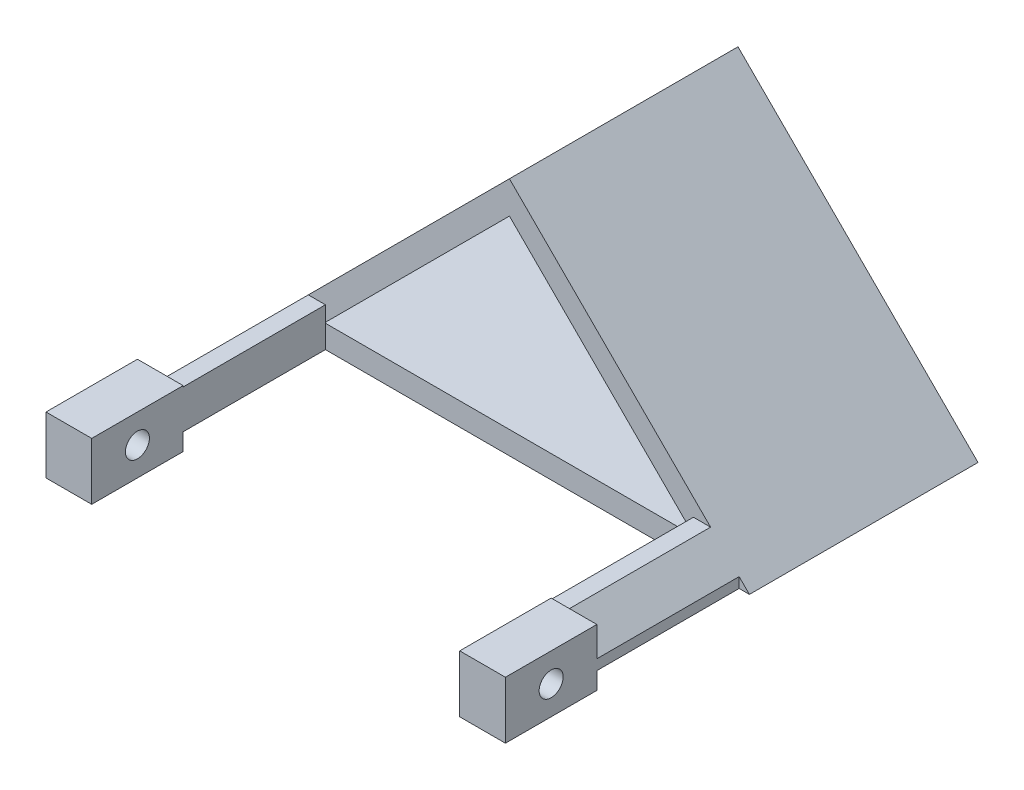
SolidWorks part; units mm, degrees
ref_plane "Front Plane" through (0, 0, 0) normal (0, 0, 1) x (1, 0, 0)
ref_plane "Top Plane" through (0, 0, 0) normal (0, 1, 0) x (1, 0, 0)
ref_plane "Right Plane" through (0, 0, 0) normal (1, 0, 0) x (0, 0, -1)
sketch "Sketch1" plane through (0, 0, 0) normal (0, 0, 1) x (1, 0, 0)
  line L1 (0, 0) -> (-42, -42)
  line L2 (0, -1000.3549) -> (0, 48999.6451) construction
  line L3 (-32.3431, -38) -> (0, -5.6569)
  line L4 (32.3431, -38) -> (0, -5.6569)
  line L5 (0, 0) -> (42, -42)
  line L7 (-42, -42) -> (42, -42)
  line L8 (-32.3431, -38) -> (32.3431, -38)
  line L9 (-34, -34) -> (34, -34) construction
  dimension "D1" = 90
  dimension "D2" = 4
  dimension "D3" = 4
  dimension "D4" = 68
  dimension "D5" = 8
extrude "Boss-Extrude1" add sketch "Sketch1" along normal mid plane 40
sketch "Sketch2" plane through (0, 0, 0) normal (1, 0, 0) x (0, 0, -1)
  line L0 (0, -1034.3624) -> (0, 48965.6376) construction
  line L1 (-20, -42) -> (20, -42) construction
  line L2 (-3.5, -42) -> (-3.5, -65.5)
  line L3 (-3.5, -65.5) -> (-9, -65.5)
  line L4 (-9, -65.5) -> (-9, -69)
  line L5 (-9, -69) -> (9, -69)
  line L6 (9, -65.5) -> (9, -69)
  line L7 (3.5, -65.5) -> (9, -65.5)
  line L8 (3.5, -42) -> (3.5, -65.5)
  line L9 (3.5, -42) -> (-3.5, -42)
  point P5 (0, -42)
  dimension "D1" = 7
  dimension "D2" = 3.5
  dimension "D3" = 27
  dimension "D4" = 18
extrude "Boss-Extrude2" [suppressed] add sketch "Sketch2" along normal blind 6 from vertex starting at point (-42, -42, 0)
sketch "Sketch4" [suppressed] plane through (0, 0, 0) normal (1, 0, 0) x (0, 0, -1)
  line L0 (-20, -38.4859) -> (20, -38.4859) construction
  line L1 (3.5, -38.4859) -> (13.5, -38.4859)
  line L2 (3.5, -38.4859) -> (3.5, -65.4859)
  line L3 (3.5, -65.4859) -> (13.5, -65.4859)
  line L4 (13.5, -38.4859) -> (13.5, -65.4859)
  line L5 (-9, -65.4859) -> (9, -65.4859) construction
  line L7 (-11, -38.4859) -> (-18.5, -38.4859)
  line L8 (-11, -38.4859) -> (-11, -65.4859)
  line L9 (-11, -65.4859) -> (-18.5, -65.4859)
  line L10 (-18.5, -38.4859) -> (-18.5, -65.4859)
  line L11 (-9, -61.9859) -> (-9, -65.4859) construction
  dimension "D1" = 10
  dimension "D2" = 2
  dimension "D3" = 7.5
extrude "Boss-Extrude3" [suppressed] add sketch "Sketch4" against normal blind 6 from vertex starting at point (42, -42, 20)
sketch "Sketch5" plane through (0, 0, 20) normal (0, 0, 1) x (1, 0, 0)
  line L1 (0, 0) -> (-42, -42) construction
  line L2 (-35.2, -35.2) -> (-32.2, -35.2)
  line L3 (-32.2, -35.2) -> (-32.2, -42)
  line L4 (-42, -42) -> (42, -42) construction
  line L5 (-32.2, -42) -> (-40.2, -42)
  line L6 (-40.2, -42) -> (-40.2, -40.2)
  line L7 (-40.2, -40.2) -> (-35.2, -35.2)
  line L9 (-40.4, 34.5736) -> (-40.4, -70) construction
  point P5 (-28.1785, -42)
  point P10 (-28.3963, -42)
  point P11 (0, 0)
  dimension "D1" = 8
  dimension "D2" = 3
  dimension "D3" = 0.2
extrude "Boss-Extrude4" add sketch "Sketch5" along normal up to surface (24.9 mm away)
sketch "Sketch6" plane through (0, 0, 44.9) normal (0, 0, 1) x (1, 0, 0)
  line L0 (-40.2, -40.2) -> (-40.2, -42) construction
  line L1 (-32.2, -45) -> (-40.2, -45)
  line L2 (-32.2, -45) -> (-32.2, -35)
  line L3 (-32.2, -35) -> (-40.2, -35)
  line L4 (-40.2, -45) -> (-40.2, -35)
  line L5 (-32.2, -42) -> (-32.2, -35.2) construction
  line L6 (-40.2, -42) -> (-32.2, -42) construction
  point P5 (-31.136, -51.2284)
  point P6 (-30.277, -57.4758)
  point P7 (0, 0)
  point P10 (-32.9605, -43.2167)
  dimension "D1" = 10
  dimension "D2" = 3
extrude "Boss-Extrude5" add sketch "Sketch6" along normal blind 16
sketch "Sketch7" plane through (-32.2, 0, 0) normal (1, 0, 0) x (0, 0, -1)
  line L0 (-60.9, -35) -> (-44.9, -35) construction
  line L1 (-60.9, -45) -> (-60.9, -35) construction
  circle A0 centre (-52.9, -40) radius 2.1
  point P2 (0, 0)
  point P5 (-52.9, -35)
  point P8 (-60.9, -40)
  dimension "D1" = 4.2
extrude "Cut-Extrude1" cut sketch "Sketch7" against normal through all
mirror "Mirror1" about plane through (0, 0, 0) normal (1, 0, 0) of "Cut-Extrude1", "Boss-Extrude5", "Boss-Extrude4"
equation "\"width\"= 24"
equation "\"thk\"= 3"
equation "\"holesize\"= 4.2"
equation "\"holedistance\"= ( 20 + 12 ) / 2"
equation "\"threaded_hole\"= 3.9"
equation "\"fillet_radius\"= 2"
equation "\"ground_clearance\"= 25"
equation "\"tire_thk\"= 3"
equation "\"innerwheel_diam\" = \"wheel_diam\"-2*\"tire_thk\""
equation "\"innerwheel_thk\"= 8"
equation "\"wheel_diam\"= 2*(\"width\"/2+\"ground_clearance\")"
equation "\"coloursensor_holesize\"= 2.65"
equation "\"hole_to_edge\" = 4"
equation "\"D1@Sketch7\"=\"holesize\""
